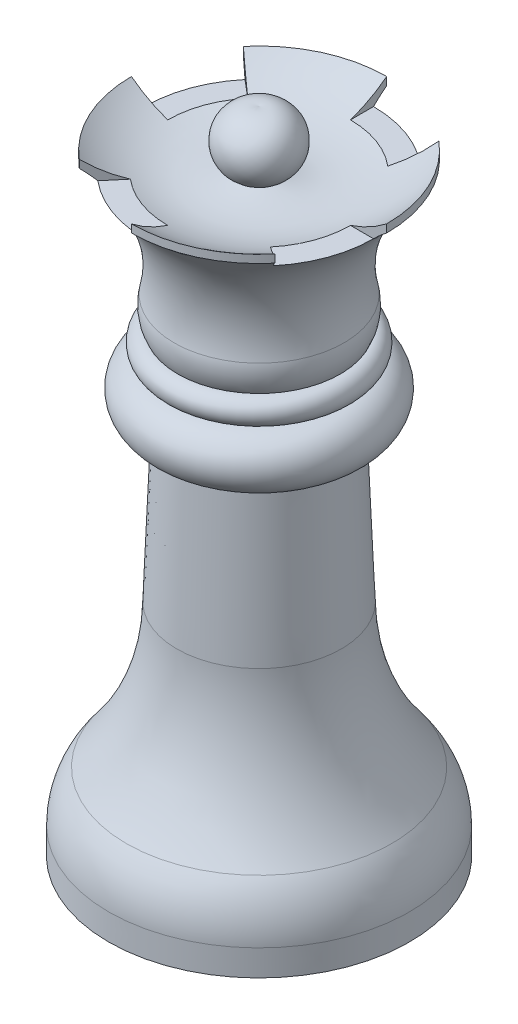
SolidWorks part; units mm, degrees
material "PVC Rigid"
ref_plane "Front Plane" through (0, 0, 0) normal (0, 0, 1) x (1, 0, 0)
ref_plane "Top Plane" through (0, 0, 0) normal (0, 1, 0) x (1, 0, 0)
ref_plane "Right Plane" through (0, 0, 0) normal (1, 0, 0) x (0, 0, -1)
sketch "Sketch1" plane through (0, 0, 0) normal (0, 0, 1) x (1, 0, 0)
  line L0 (0, 0) -> (-11.6, 0)
  line L3 (-11.5897, 2) -> (-11.6, 0)
  line L32 (0, 50) -> (0, 0)
  line L33 (-5.8734, 29.12) -> (-6.3432, 29.12)
  line L34 (-6.3432, 16.936) -> (-5.8734, 29.12)
  line L35 (-9.8373, 46.4466) -> (-9.8373, 47.061)
  line L36 (0, 0) -> (0, 50) construction
  arc A0 (-10.2296, 5.8838) -> (-11.5897, 2) centre (-5.271, 1.9673) ccw
  circle A32 centre (0, 47.5962) radius 2.4038 construction
  arc A34 (0, 50) -> (-1.2079, 45.5179) centre (-0.4218, 47.7099) ccw
  arc A36 (-6.3432, 29.12) -> (-6.2866, 33.2698) centre (-6.3432, 31.1953) cw
  arc A39 (-9.8373, 46.4466) -> (-6.5463, 37.467) centre (-15.0641, 39.4381) cw
  arc A40 (-10.2296, 5.8838) -> (-6.3432, 16.936) centre (-24.3998, 17.076) ccw
  arc A42 (-9.8373, 47.061) -> (-1.2079, 45.5179) centre (-4.0599, 54.4691) ccw
  arc A43 (-6.2866, 33.2698) -> (-6.2597, 35.24) centre (-6.2598, 34.2547) cw
  arc A44 (-6.5463, 37.467) -> (-6.2597, 35.24) centre (-3.4026, 36.7396) ccw
  point P18 (0, 0)
  point P19 (0, 0)
  point P21 (-4.3463, 39.2206)
  point P23 (0, 0)
  dimension "D2" = 5.8734
  dimension "D6" = 4.1499
  dimension "D4" = 50
  dimension "D8" = 3.2268
  dimension "D9" = 8.7429
  dimension "D11" = 16.3979
  dimension "D13" = 20.88
  dimension "D15" = 17.941
  dimension "D16" = 2.0753
  dimension "D17" = 6.2866
  dimension "D19" = 8.3471
  dimension "D23" = 10.2296
  dimension "D21" = 5.8838
  dimension "D18" = 6.5463
  dimension "D20" = 9.3945
  dimension "D35" = 2.3287
  dimension "D7" = 0.9853
  dimension "D22" = 6.3187
  dimension "D1" = 2
  dimension "D5" = 11.6
  dimension "D10" = 0.6144
  dimension "D12" = 1.2079
  dimension "D14" = 8.6293
revolve "Revolve6" add sketch "Sketch1" angle 360 about L32 region at (-3.8926, 21.7552, 0)
sketch "Sketch10" plane through (0, 0, 0) normal (0, 0, 1) x (1, 0, 0)
  line L0 (-9.8373, 48.8388) -> (-9.8373, 47.061) construction
  line L1 (-14.5937, 48.8388) -> (-5.0809, 48.8388)
  line L2 (-14.5937, 48.8388) -> (-14.5937, 45.561)
  line L3 (-14.5937, 45.561) -> (-5.0809, 45.561)
  line L4 (-5.0809, 48.8388) -> (-5.0809, 45.561)
  point P7 (-9.8373, 45.561)
  point P8 (-5.0809, 45.561)
  dimension "D1" = 1.5
revolve "Cut-Revolve8" cut sketch "Sketch10" angle 40 about L36 reverse direction yes
sketch "Sketch11" plane through (0, 0, 0) normal (0, 0, 1) x (1, 0, 0)
  line L0 (9.8373, 49.9649) -> (9.8373, 47.061) construction
  line L1 (6.3584, 49.9649) -> (13.3161, 49.9649)
  line L2 (6.3584, 49.9649) -> (6.3584, 45.561)
  line L3 (6.3584, 45.561) -> (13.3161, 45.561)
  line L4 (13.3161, 49.9649) -> (13.3161, 45.561)
  line L5 (-9.8373, 47.061) -> (9.8373, 47.061) construction
  dimension "D1" = 1.5
revolve "Cut-Revolve9" cut sketch "Sketch11" angle 40 about L36 reverse direction yes
sketch "Sketch12" plane through (0, 0, 0) normal (1, 0, 0) x (0, 0, -1)
  line L0 (9.8373, 48.8989) -> (9.8373, 47.061) construction
  line L1 (5.2356, 48.8989) -> (14.4389, 48.8989)
  line L2 (5.2356, 48.8989) -> (5.2356, 45.561)
  line L3 (5.2356, 45.561) -> (14.4389, 45.561)
  line L4 (14.4389, 48.8989) -> (14.4389, 45.561)
  line L5 (0, 47.061) -> (9.8373, 47.061) construction
  dimension "D1" = 1.5
revolve "Cut-Revolve10" cut sketch "Sketch12" angle 40 about L36 reverse direction yes
sketch "Sketch13" plane through (0, 0, 0) normal (1, 0, 0) x (0, 0, -1)
  line L0 (-9.8373, 48.6739) -> (-9.8373, 47.061) construction
  line L1 (-14.1563, 48.6739) -> (-5.5182, 48.6739)
  line L2 (-14.1563, 48.6739) -> (-14.1563, 45.561)
  line L3 (-14.1563, 45.561) -> (-5.5182, 45.561)
  line L4 (-5.5182, 48.6739) -> (-5.5182, 45.561)
  line L5 (0, 47.061) -> (-9.8373, 47.061) construction
  point P8 (-9.8373, 45.561)
  dimension "D1" = 1.5
revolve "Cut-Revolve11" cut sketch "Sketch13" angle 40 about L36 reverse direction yes
sketch "Sketch8" plane through (0, 0, 0) normal (0, -1, 0) x (1, 0, 0)
  circle A0 centre (0, 0) radius 10
extrude "Cut-Extrude1" cut sketch "Sketch8" against normal blind 2 from offset 0.4 offset against normal yes
